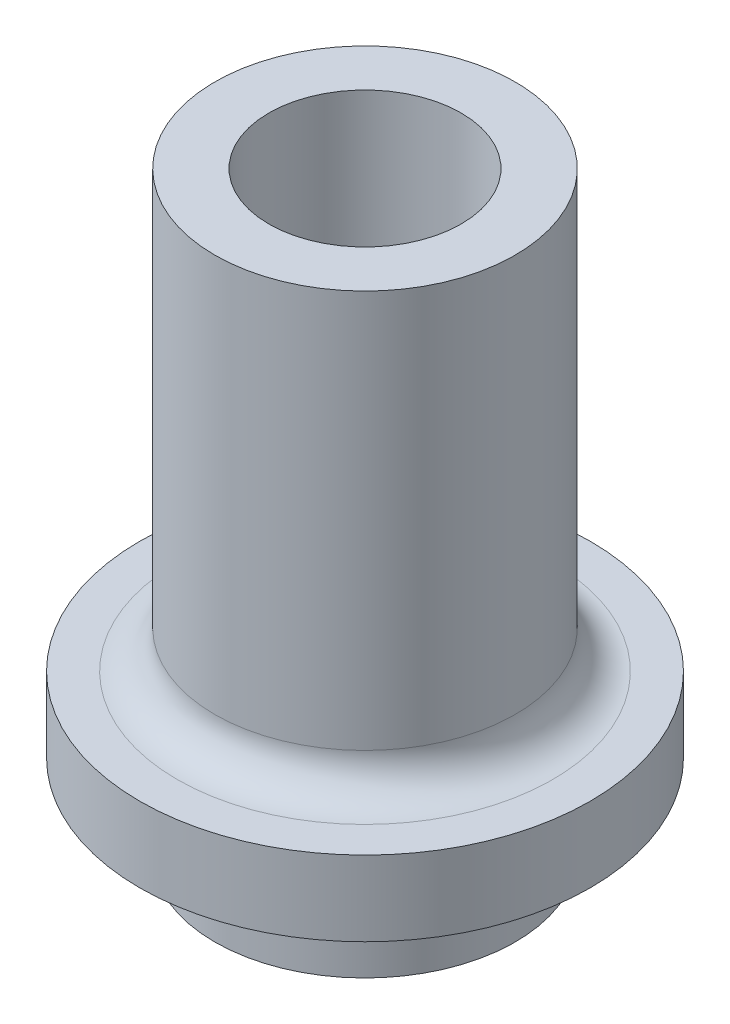
SolidWorks part; units mm, degrees
ref_plane "Front" through (0, 0, 0) normal (0, 0, 1) x (1, 0, 0)
ref_plane "Top" through (0, 0, 0) normal (0, 1, 0) x (1, 0, 0)
ref_plane "Right" through (0, 0, 0) normal (1, 0, 0) x (0, 0, -1)
sketch "Sketch1" plane through (0, 0, 0) normal (0, 1, 0) x (1, 0, 0)
  line L0 (-1.12, 1.057) -> (1.12, 1.057)
  circle A0 centre (0, 0) radius 4
  arc A1 (-1.12, 1.057) -> (1.12, 1.057) centre (0, 0) ccw
  dimension "D1" = 3.08
  dimension "D3" = 8
  dimension "D2" = 2.24
extrude "Boss-Extrude1" add sketch "Sketch1" along normal blind 9.25
sketch "Sketch2" plane through (0, 9.25, 0) normal (0, 1, 0) x (1, 0, 0)
  circle A0 centre (0, 0) radius 4
  circle A1 centre (0, 0) radius 4 construction
extrude "Boss-Extrude2" add sketch "Sketch2" along normal blind 1
sketch "Sketch3" plane through (0, 10.25, 0) normal (0, 1, 0) x (1, 0, 0)
  circle A0 centre (0, 0) radius 2.5625
  circle A2 centre (0, 0) radius 4
  circle A3 centre (0, 0) radius 4
  dimension "D1" = 5.125
  dimension "D2" = 0
extrude "Boss-Extrude3" add sketch "Sketch3" along normal blind 5.6
sketch "Sketch5" plane through (0, 2.25, 0) normal (0, 1, 0) x (1, 0, 0)
  line L0 (1.12, 1.057) -> (-1.12, 1.057) construction
  line L1 (1.12, 1.057) -> (-1.12, 1.057)
  circle A0 centre (0, 0) radius 6
  arc A1 (-1.12, 1.057) -> (1.12, 1.057) centre (0, 0) ccw construction
  arc A2 (-1.12, 1.057) -> (1.12, 1.057) centre (0, 0) ccw
  dimension "D1" = 12
extrude "Boss-Extrude4" add sketch "Sketch5" along normal blind 2
fillet "Fillet1" radius 1 1 edges at (0, 4.25, 4)
